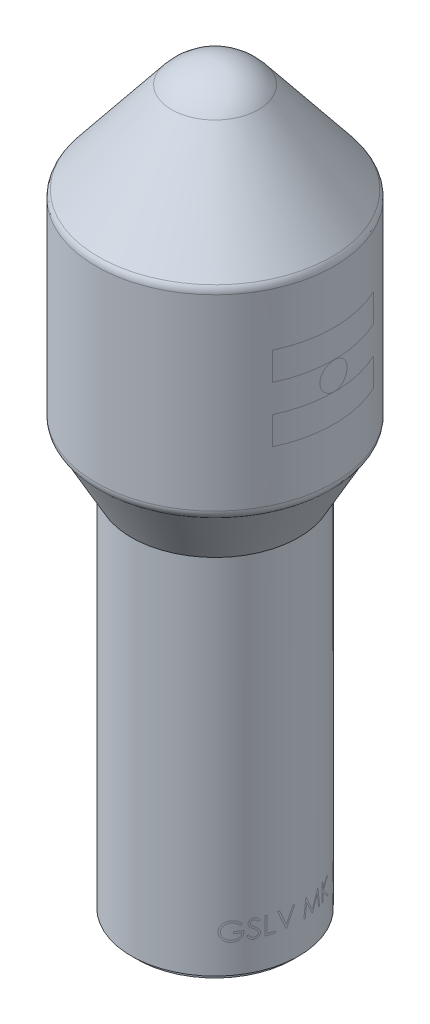
SolidWorks part; units mm, degrees
ref_plane "Front Plane" through (0, 0, 0) normal (0, 0, 1) x (1, 0, 0)
ref_plane "Top Plane" through (0, 0, 0) normal (0, 1, 0) x (1, 0, 0)
ref_plane "Right Plane" through (0, 0, 0) normal (1, 0, 0) x (0, 0, -1)
sketch "Sketch1" plane through (0, 0, 0) normal (0, 0, 1) x (1, 0, 0)
  line L0 (0, 32.2273) -> (0, 168.7873)
  line L1 (7.8018, 165.0428) -> (20.89, 148.7196)
  line L2 (21.3296, 147.4685) -> (21.3296, 113.8879)
  line L3 (15, 102.211) -> (15, 37.211)
  line L4 (20.6003, 112.3435) -> (15, 102.211)
  line L9 (15, 37.211) -> (14, 37.211)
  line L10 (14, 37.211) -> (14, 36.211)
  arc A0 (0, 168.7873) -> (7.8018, 165.0428) centre (0, 158.7873) cw
  arc A1 (20.89, 148.7196) -> (21.3296, 147.4685) centre (19.3296, 147.4685) cw
  arc A2 (21.3296, 113.8879) -> (20.6003, 112.3435) centre (19.3296, 113.8879) cw
  spline S0 degree 3 poles (14, 36.211) (11.2243, 34.8235) (0.9782, 32.1703) (0, 32.2273) knots 0 0 0 0 1 1 1 1
  dimension "D1" = 10
  dimension "D3" = 2
  dimension "D4" = 2
  dimension "D2" = 20.89
  dimension "D5" = 136.56
  dimension "D6" = 65
  dimension "D7" = 15
  dimension "D8" = 1
  dimension "D9" = 1
revolve "Revolve1" add sketch "Sketch1" angle 360 about L0
ref_plane "Plane1" through (50, 0, 0) normal (1, 0, 0) x (0, 0, -1)
sketch "Sketch2" plane through (50, 0, 0) normal (1, 0, 0) x (0, 0, -1)
  line L1 (-9.3141, 137.9685) -> (9.377, 137.9685)
  line L2 (-9.3141, 137.9685) -> (-9.3141, 132.9685)
  line L3 (-9.3141, 132.9685) -> (9.377, 132.9685)
  line L4 (9.377, 137.9685) -> (9.377, 132.9685)
  line L5 (-9.3141, 127.9685) -> (9.377, 127.9685)
  line L6 (-9.3141, 127.9685) -> (-9.3141, 122.9685)
  line L7 (-9.3141, 122.9685) -> (9.377, 122.9685)
  line L8 (9.377, 127.9685) -> (9.377, 122.9685)
  circle A1 centre (0.0315, 130.4685) radius 2.45
  dimension "D5" = 4.9
  dimension "D1" = 5
  dimension "D2" = 5
  dimension "D3" = 5
wrap "Wrap1" sketch "Sketch2" wrap type scribe source sketch "Sketch2"
ref_plane "Plane2" through (50, 0, 0) normal (1, 0, 0) x (0, 0, -1)
sketch "Sketch7" plane through (50, 0, 0) normal (1, 0, 0) x (0, 0, -1)
  text T0 "GSLV MK III" font "Century Gothic" height 3.175
wrap "Wrap2" sketch "Sketch7" wrap type scribe source sketch "Sketch7"
ref_plane "Plane3" through (21.5, 0, 0) normal (1, 0, 0) x (0, 0, -1)
